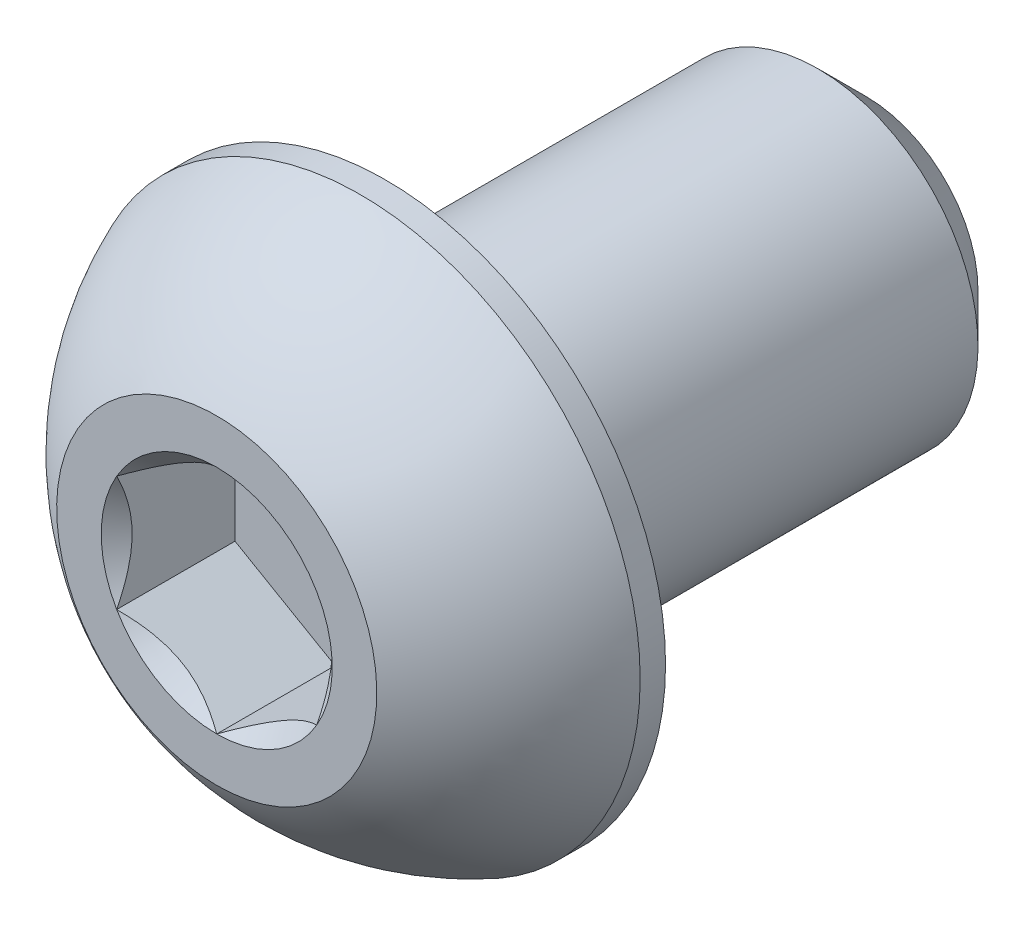
SolidWorks part; units mm, degrees
ref_plane "Front" through (0, 0, 0) normal (0, 0, 1) x (1, 0, 0)
ref_plane "Top" through (0, 0, 0) normal (0, 1, 0) x (1, 0, 0)
ref_plane "Right" through (0, 0, 0) normal (1, 0, 0) x (0, 0, -1)
sketch "Sketch1" plane through (0, 0, 0) normal (1, 0, 0) x (0, 0, -1)
  line L2 (3.3528, 3.175) -> (12.8778, 3.175)
  line L3 (12.8778, 3.175) -> (12.8778, 0)
  line L4 (12.8778, 0) -> (3.3528, 0)
  line L6 (2.8499, 5.5499) -> (3.3528, 5.5499) construction
  line L7 (12.8778, 3.175) -> (12.8778, -3.175) construction
  line L8 (0, 0) -> (3.3528, 0) construction
  line L9 (3.3528, 5.5499) -> (3.3528, -5.5499) construction
  line L11 (3.3528, 3.175) -> (3.3528, 0)
  line L13 (0, 1.9844) -> (0, -1.9844) construction
  line L14 (0, 1.9844) -> (0, 3.175) construction
  arc A3 (0, 3.175) -> (2.8499, 5.5499) centre (5.0603, 0) cw construction
  dimension "D1" = 0.5029
revolve "Revolve1" add sketch "Sketch1" angle 360 mid plane about L4
sketch "Sketch3" plane through (0, 0, -12.8778) normal (0, 0, -1) x (-1, 0, 0)
  circle A0 centre (0, 0) radius 3.175
curve "Helix/Spiral1" pitch 1.27 height 10.795 turns 8.5
sketch "Sketch2" plane through (0, 0, 0) normal (1, 0, 0) x (0, 0, -1)
  line L0 (12.8778, 3.175) -> (13.989, 3.175)
  line L1 (13.989, 3.175) -> (13.5128, 2.3501)
  line L2 (13.5128, 2.3501) -> (13.354, 2.3501)
  line L3 (13.354, 2.3501) -> (12.8778, 3.175)
  line L4 (13.1159, 2.7626) -> (13.7509, 2.7626) construction
  dimension "D1" = 60
  dimension "D2" = 0.1588
  dimension "D3" = 0.635
chamfer "Chamfer1" distance 0.9525 angle 45 1 edges at (0, 3.175, -12.8778)
sweep "Cut-Sweep1" [suppressed] cut profiles "Sketch2" path "Helix/Spiral1"
sketch "Sketch7" plane through (0, 0, 0) normal (1, 0, 0) x (0, 0, -1)
  line L6 (2.8499, 5.5499) -> (3.3528, 5.5499) construction
  line L8 (0, 0) -> (3.3528, 0) construction
  line L11 (3.3528, 5.5499) -> (3.3528, -5.5499) construction
  line L12 (2.8499, 5.5499) -> (3.3528, 5.5499)
  line L13 (0, 0) -> (3.3528, 0)
  line L14 (0, 1.9844) -> (0, -1.9844) construction
  line L15 (3.3528, 5.5499) -> (3.3528, 0)
  line L16 (0, 3.175) -> (0, 0)
  arc A2 (2.8499, 5.5499) -> (0, 3.175) centre (5.0603, 0) ccw construction
  arc A3 (2.8499, 5.5499) -> (0, 3.175) centre (5.0603, 0) ccw
revolve "Revolve2" add sketch "Sketch7" angle 360 mid plane about L13
sketch "Sketch5" plane through (0, 0, 0) normal (0, 0, 1) x (1, 0, 0)
  line L1 (1.9844, -1.1457) -> (1.9844, 1.1457)
  line L2 (1.9844, 1.1457) -> (0, 2.2914)
  line L3 (0, 2.2914) -> (-1.9844, 1.1457)
  line L4 (-1.9844, 1.1457) -> (-1.9844, -1.1457)
  line L5 (-1.9844, -1.1457) -> (0, -2.2914)
  line L6 (0, -2.2914) -> (1.9844, -1.1457)
  circle A0 centre (0, 0) radius 1.9844 construction
extrude "Cut-Extrude2" cut sketch "Sketch5" against normal blind 2.347
sketch "Sketch6" plane through (0, 0, 0) normal (0, 0, 1) x (1, 0, 0)
  circle A0 centre (0, 0) radius 2.2914
extrude "Cut-Extrude3" cut sketch "Sketch6" against normal blind 2.347 draft 45
sketch "Sketch9" [suppressed] plane through (0, 0, -3.3528) normal (0, 0, 1) x (1, 0, 0)
  circle A2 centre (0, 0) radius 3.175
extrude "Boss-Extrude2" [suppressed] add sketch "Sketch9" against normal offset from surface (6.35 mm away) 22.225
sketch "Sketch10" plane through (0, 0, 0) normal (1, 0, 0) x (0, 0, -1)
  line L0 (12.8778, 3.175) -> (12.8778, -3.175) construction
  point P0 (10.9728, -3.175)
  dimension "D1" = 1.905
equation "\"D3@Helix/Spiral1\" = \"Lg@Sketch1\" + \"D4@Helix/Spiral1\""
equation "\"D2@Sketch2\" = \"D4@Helix/Spiral1\" * .125"
equation "\"D3@Sketch2\" = \"D4@Helix/Spiral1\" * .5"
equation "\"D1@Chamfer1\" = \"D4@Helix/Spiral1\" * .75"
equation "\"D1@Cut-Extrude2\" = \"Head Ht@Sketch1\" * .7"
equation "\"D1@Sketch1\" = \"Head Ht@Sketch1\" * .15"
equation "\"D1@Sketch10\" = \"D4@Helix/Spiral1\" * 1.5"
equation "\"D1@Cut-Extrude3\" = \"D1@Cut-Extrude2\""
